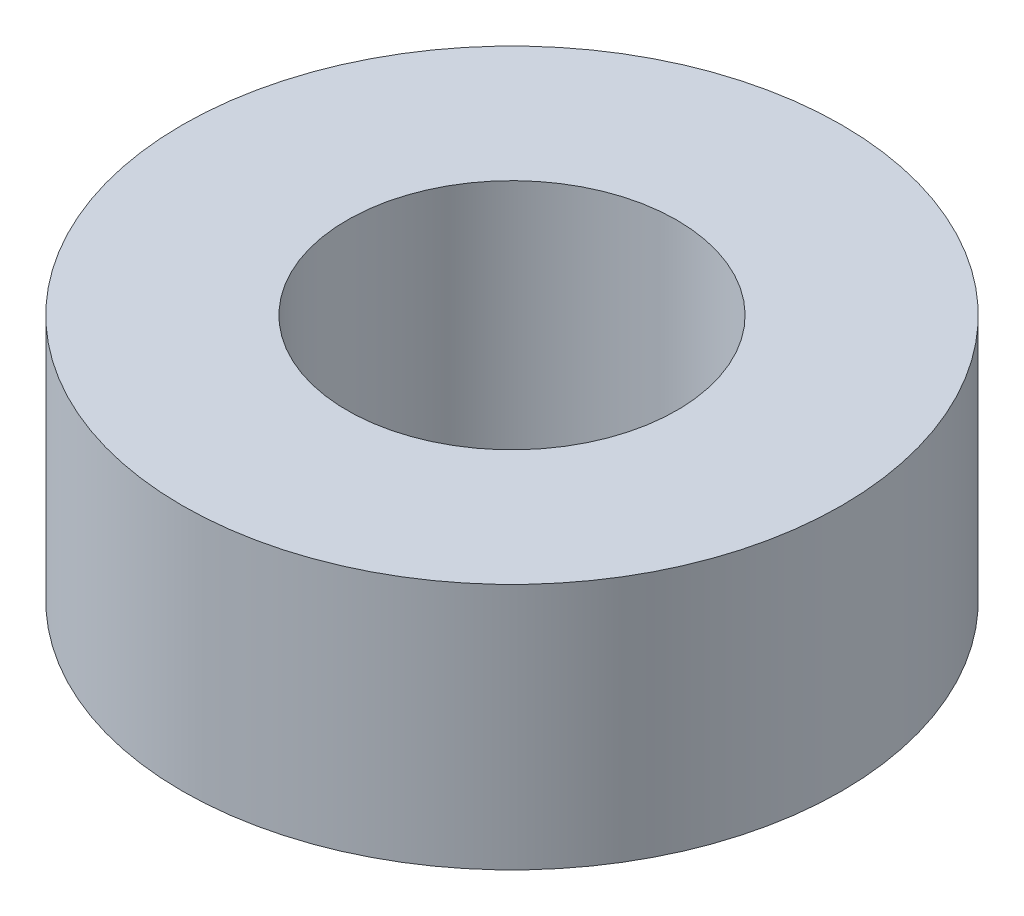
SolidWorks part; units mm, degrees
ref_plane "Front" through (0, 0, 0) normal (0, 0, 1) x (1, 0, 0)
ref_plane "Top" through (0, 0, 0) normal (0, 1, 0) x (1, 0, 0)
ref_plane "Right" through (0, 0, 0) normal (1, 0, 0) x (0, 0, -1)
sketch "Sketch1" plane through (0, 0, 0) normal (0, 1, 0) x (1, 0, 0)
  circle A1 centre (0, 0) radius 3.175
  circle A2 centre (0, 0) radius 6.35
  dimension "D2" = 3.175
  dimension "D1" = 6.35
extrude "Boss-Extrude2" add sketch "Sketch1" along normal blind 4.7625
